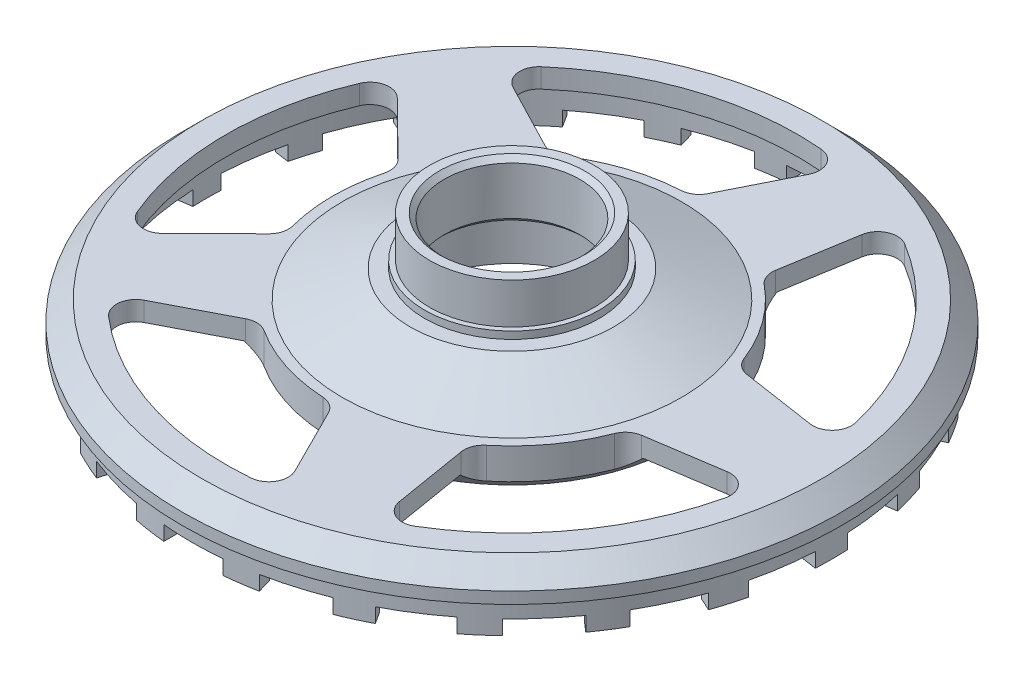
SolidWorks part; units mm, degrees
ref_plane "Front Plane" through (0, 0, 0) normal (0, 0, 1) x (1, 0, 0)
ref_plane "Top Plane" through (0, 0, 0) normal (0, 1, 0) x (1, 0, 0)
ref_plane "Right Plane" through (0, 0, 0) normal (1, 0, 0) x (0, 0, -1)
ref_axis "Axis1" through (0, 0, 0) along (0, 1, 0)
sketch "Sketch1" plane through (0, 0, 0) normal (0, 0, 1) x (1, 0, 0)
  line L0 (-33, 8) -> (-33, 4.5)
  line L2 (-33, 4.5) -> (-31.5, 4.5)
  line L3 (-31.5, 4.5) -> (-31.5, 8.2)
  line L4 (-33, 8) -> (-34, 8)
  line L5 (-34, 8) -> (-34, 8.5)
  line L7 (-10.5, 14) -> (-9, 14)
  line L8 (-9, 14) -> (-9, 14.75)
  line L9 (-9, 14.75) -> (-8.5, 14.75)
  line L10 (-8.5, 14.75) -> (-8.5, 18.95)
  line L11 (-8.5, 18.95) -> (-7, 18.95)
  line L12 (-7, 18.95) -> (-7, 13)
  line L15 (0, 0) -> (0, -50000) construction
  line L16 (-30.5, 9.2) -> (-31.5, 8.2)
  line L18 (-10.5, 12) -> (-10.5, 7)
  line L21 (-7, 13) -> (-9.5, 13)
  line L25 (15.5305, 6) -> (-16, 6) construction
  line L26 (-10.5, 12) -> (-9.5, 12)
  line L27 (-9.5, 12) -> (-9.5, 13)
  line L29 (-19.7, 9.2) -> (-30.5, 9.2)
  line L32 (-34, 9.2) -> (-34, 8.5)
  line L34 (-32, 11.2) -> (-17.5, 11.2)
  line L35 (-34, 9.2) -> (-32, 11.2)
  line L36 (-10.5, 14) -> (-17.5, 11.2)
  line L38 (19.25, 6) -> (-19.25, 6) construction
  line L39 (-19.7, 9.2) -> (-17.5, 7)
  line L40 (-17.5, 7) -> (-10.5, 7)
  point P2 (0, 0)
  point P3 (0, 0)
  point P6 (-31.5, 9.2)
  point P18 (-17.5, 11.6407)
  point P19 (-34, 11.2)
  point P27 (0, 0)
  dimension "D1" = 3.5
  dimension "D2" = 1.5
  dimension "D3" = 17
  dimension "D4" = 4.2
  dimension "D5" = 0.75
  dimension "D6" = 0.5
  dimension "D7" = 1.5
  dimension "D8" = 1
  dimension "D9" = 8
  dimension "D10" = 66
  dimension "D11" = 7
  dimension "D12" = 21
  dimension "D14" = 1
  dimension "D15" = 5
  dimension "D18" = 0.5
  dimension "D19" = 2
  dimension "D20" = 3.2
  dimension "D21" = 1
  dimension "D22" = 135
revolve "Revolve1" add sketch "Sketch1" angle 360 about L15
sketch "Sketch2" plane through (0, 0, 0) normal (0, 0, 1) x (1, 0, 0)
  line L1 (-3.05, -0.7629) -> (3.05, -0.7629)
  line L2 (-3.05, -0.7629) -> (-3.05, 6)
  line L3 (-3.05, 6) -> (3.05, 6)
  line L4 (3.05, -0.7629) -> (3.05, 6)
  line L5 (-33, 8) -> (33, 8) construction
  point P4 (0, -0.7629)
  dimension "D1" = 6.1
  dimension "D2" = 2
extrude "Cut-Extrude2" cut sketch "Sketch2" along normal through all from offset 20
pattern_circular "CirPattern1" count 22 over 360 about axis through (0, 0, 0) along (0, 1, 0) of "Cut-Extrude2"
sketch "Sketch4" plane through (0, 0, 0) normal (0, 1, 0) x (1, 0, 0)
  circle A0 centre (-14.5, 0) radius 2.06
  dimension "D1" = 4.12
  dimension "D2" = 14.5
extrude "Cut-Extrude3" cut sketch "Sketch4" along normal blind 3 from surface starting at face at (0, 7, 10.5)
pattern_circular "CirPattern2" count 24 over 360 about axis through (0, 0, 0) along (0, 1, 0) of "Cut-Extrude3"
sketch "Sketch5" plane through (0, 0, 0) normal (0, 1, 0) x (1, 0, 0)
  circle A0 centre (0, 0) radius 14.5
extrude "Cut-Extrude-Thin1" cut sketch "Sketch5" along normal up to surface (10 mm away) thin up to face at (0, 10, 0) thin type mid plane wall 1.5
chamfer "Chamfer1" distance 0.5 angle 45 2 edges at (0, 18.95, 7) (0, 13, 7)
sketch "Sketch6" plane through (0, 0, 0) normal (0, 1, 0) x (1, 0, 0)
  line L0 (0, 0) -> (-50000, 0) construction
  line L1 (-25.9264, -14.0738) -> (-17.5608, -5.8198)
  line L2 (-17.5608, 5.8198) -> (-25.9264, 14.0738)
  arc A0 (-25.9264, -14.0738) -> (-25.9264, 14.0738) centre (0, 0) cw
  arc A1 (-17.5608, -5.8198) -> (-17.5608, 5.8198) centre (0, 0) cw
  circle A2 centre (0, 0) radius 30.5 construction
  point P9 (-29.5, 0)
  point P10 (-18.5, 0)
  dimension "D1" = 1
extrude "Cut-Extrude4" cut sketch "Sketch6" along normal through all
fillet "Fillet1" radius 2 4 edges at (-25.9264, 10.2, 14.0738) (-17.5608, 9.6, 5.8198) (-17.5608, 9.6, -5.8198) (-25.9264, 10.2, -14.0738)
pattern_circular "CirPattern3" count 5 over 360 about axis through (0, 0, 0) along (0, 1, 0) of "Cut-Extrude4", "Fillet1"
